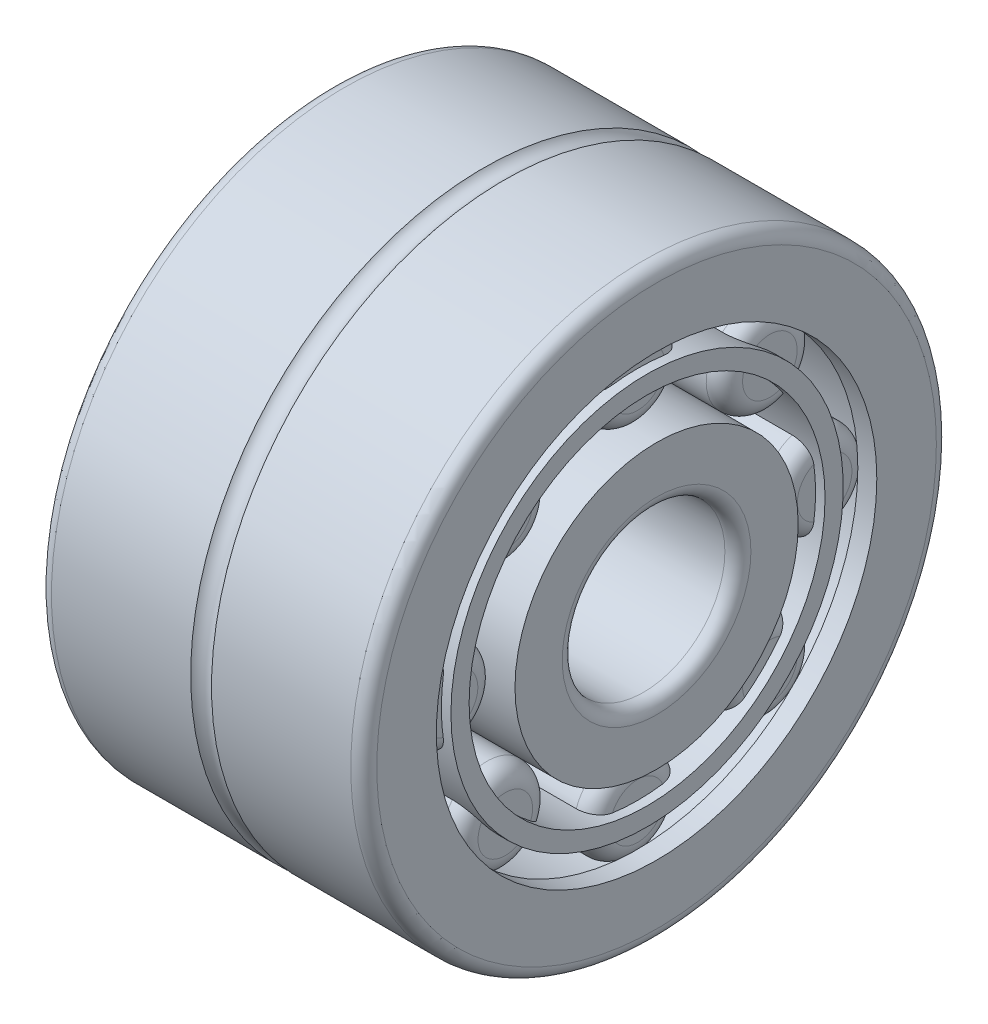
SolidWorks part; units mm, degrees
ref_plane "Plane1" through (0, 0, 0) normal (0, 0, 1) x (1, 0, 0)
ref_plane "Plane2" through (0, 0, 0) normal (0, 1, 0) x (1, 0, 0)
ref_plane "Plane3" through (0, 0, 0) normal (1, 0, 0) x (0, 0, -1)
sketch "Clipboard" plane through (0, 0, 0) normal (0, 0, 1) x (1, 0, 0)
  line L0 (-10, 0) -> (10, 0) construction
  line L1 (0, 0) -> (27.3694, -3.8465)
  line L2 (0, 0) -> (36.1572, 5.0816)
  line L3 (0, 0) -> (44.9449, -6.3166)
  line L4 (0, 0) -> (-22.3471, -0.7804)
  dimension "Race_OD" = 45.3866
  dimension "Race_ID" = 27.6384
sketch "OutRacSke" plane through (0, 0, 0) normal (0, 0, 1) x (1, 0, 0)
  line L0 (-14.0229, 22.6933) -> (-14.0229, 21.4933)
  line L1 (-14.0229, 21.4933) -> (-15.875, 21.4933)
  line L2 (-15.875, 21.4933) -> (-15.875, 27.305)
  line L3 (-14.605, 28.575) -> (-1.016, 28.575)
  line L4 (15.875, 27.305) -> (15.875, 21.4933)
  line L5 (15.875, 21.4933) -> (14.0229, 21.4933)
  line L6 (14.0229, 21.4933) -> (14.0229, 22.6933)
  line L7 (14.0229, 22.6933) -> (-14.0229, 22.6933)
  line L8 (-7.9375, 0) -> (7.9375, 0) construction
  line L9 (1.016, 28.575) -> (14.605, 28.575)
  arc A0 (-15.875, 27.305) -> (-14.605, 28.575) centre (-14.605, 27.305) cw
  arc A1 (14.605, 28.575) -> (15.875, 27.305) centre (14.605, 27.305) cw
  arc A2 (-1.016, 28.575) -> (1.016, 28.575) centre (0, 29.337) ccw
  dimension "D1" = 14.0229
  dimension "Groove_Dp" = 1.2
  dimension "Race_OD" = 45.3866
  dimension "D2" = 0.762
  dimension "Cyl_Len" = 28.0458
  dimension "halfWidth" = 15.875
revolve "OuterRace" add sketch "OutRacSke" angle 360 about L8 reverse direction yes
sketch "RolDetSke" plane through (0, 0, 0) normal (0, 0, 1) x (1, 0, 0)
  line L0 (-14.0229, 20.9188) -> (-14.0229, 18.2562)
  line L1 (-14.0229, 18.2562) -> (14.0229, 18.2562)
  line L2 (14.0229, 18.2562) -> (14.0229, 20.9188)
  line L3 (12.2479, 22.6938) -> (-12.2479, 22.6938)
  line L4 (-28.575, 18.2562) -> (28.575, 18.2562) construction
  arc A0 (14.0229, 20.9188) -> (12.2479, 22.6938) centre (12.2479, 20.9188) ccw
  arc A1 (-12.2479, 22.6938) -> (-14.0229, 20.9188) centre (-12.2479, 20.9188) ccw
  dimension "Cyl_Len" = 28.0458
  dimension "radius" = 1.775
  dimension "Roller_diameter" = 8.8751
revolve "RollerDetailed" add sketch "RolDetSke" angle 360 about L4 reverse direction yes
ref_axis "Axis1" through (-50, 0, 0) along (1, 0, 0)
sketch "RolSimSke" plane through (0, 25.4, 0) normal (0, 0, 1) x (1, 0, 0)
  line L0 (-14.0229, -4.4807) -> (-14.0229, -9.8058)
  line L1 (-25.4, -25.4) -> (25.4, -25.4) construction
  line L2 (14.0229, -9.8058) -> (14.0229, -4.4807)
  line L3 (12.2479, -2.7057) -> (-12.2479, -2.7057)
  line L5 (12.2479, -11.5808) -> (-12.2479, -11.5808)
  arc A0 (14.0229, -4.4807) -> (12.2479, -2.7057) centre (12.2479, -4.4807) ccw
  arc A1 (-12.2479, -2.7057) -> (-14.0229, -4.4807) centre (-12.2479, -4.4807) ccw
  arc A2 (14.0229, -9.8058) -> (12.2479, -11.5808) centre (12.2479, -9.8058) cw
  arc A3 (-12.2479, -11.5808) -> (-14.0229, -9.8058) centre (-12.2479, -9.8058) cw
  dimension "radius" = 1.775
  dimension "Roller_diameter" = 8.8751
  dimension "Cyl_Len" = 28.0458
revolve "RollersSimplified" [suppressed] add sketch "RolSimSke" angle 360 about L1
sketch "InsRacSke" plane through (0, 0, 0) normal (0, 0, 1) x (1, 0, 0)
  line L2 (-15.875, 13.8192) -> (-15.875, 9.2075)
  line L4 (-14.605, 7.9375) -> (14.605, 7.9375)
  line L5 (15.875, 9.2075) -> (15.875, 13.8192)
  line L8 (15.875, 13.8192) -> (-15.875, 13.8192)
  line L9 (-7.9375, 0) -> (7.9375, 0) construction
  arc A0 (-15.875, 9.2075) -> (-14.605, 7.9375) centre (-14.605, 9.2075) ccw
  arc A2 (14.605, 7.9375) -> (15.875, 9.2075) centre (14.605, 9.2075) ccw
  dimension "radius" = 1.27
  dimension "Bore" = 15.875
  dimension "halfWidth" = 15.875
  dimension "Race_ID" = 27.6384
revolve "InnerRace" add sketch "InsRacSke" angle 360 about L9 reverse direction yes
sketch "CagSpiSke" plane through (0, 0, 0) normal (0, 0, 1) x (1, 0, 0)
  line L0 (-17.1595, 0) -> (17.1595, 0) construction
  line L3 (-14.949, 17.3687) -> (14.949, 17.3687)
  line L4 (-14.949, 17.3687) -> (-14.949, 19.1438)
  line L5 (-14.949, 19.1438) -> (14.949, 19.1438)
  line L6 (14.949, 17.3687) -> (14.949, 19.1438)
revolve "CageSpine" add sketch "CagSpiSke" angle 360 about L0
pattern_circular "RollersDetailed" count 8 every 45 about axis through (-50, 0, 0) along (1, 0, 0) of "RollerDetailed"
equation "\"halfWidth@OutRacSke\" =  \"Width@OutRacSke\" / 2"
equation "\"CLdia@Clipboard\" =  ( \"Race_OD@Clipboard\" + \"Race_ID@Clipboard\" )  / 2"
equation "\"CLRad@RolDetSke\" = ( \"Race_OD@Clipboard\" + \"Race_ID@Clipboard\" )  / 4"
equation "\"Roller_diameter@RolDetSke\" =  ( \"Race_OD@Clipboard\" -  \"Race_ID@Clipboard\" )  / 2 + .001"
equation "\"Roller_diameter@RolSimSke\" = ( \"Race_OD@Clipboard\" -  \"Race_ID@Clipboard\" )  / 2 + .001"
equation "\"radius@RolDetSke\" = \"Roller_diameter@RolDetSke\" / 5"
equation "\"radius@RolSimSke\" = \"Roller_diameter@RolSimSke\" / 5"
equation "\"Cyl_Len@OutRacSke\" = \"Cyl_Len@RolDetSke\""
equation "\"Cyl_Len@RolSimSke\" = \"Cyl_Len@RolDetSke\""
equation "\"halfCylLen@RolDetSke\" = \"Cyl_Len@RolDetSke\" / 2"
equation "\"D1@OutRacSke\" = \"Cyl_Len@OutRacSke\" / 2"
equation "\"D2@OutRacSke\" = \"Radius@OutRacSke\" * .6"
equation "\"cage_width@CagSpiSke\" =  ( \"Cyl_Len@RolDetSke\" + \"Width@OutRacSke\" )  / 2"
equation "\"halfwidth@CagSpiSke\" = \"cage_width@CagSpiSke\" / 2"
equation "\"cage_thickness@CagSpiSke\" = \"Roller_diameter@RolDetSke\" / 5"
equation "\"d2@CagSpiSke\" = \"CLRad@RolDetSke\" * 2 - \"cage_thickness@CagSpiSke\""
equation "\"Max_count@Clipboard\" = int( 3.14159265 / atn(( \"Roller_diameter@RolDetSke\" / 2) / sqr( \"CLRad@RolDetSke\"  *  \"CLRad@RolDetSke\" - ( \"Roller_diameter@RolDetSke\" / 2) *  ( \"Roller_diameter@RolDetSke\" / 2))))"
equation "\"Max_count@Clipboard\" = ((sgn( \"Max_count@Clipboard\" - \"Count@Clipboard\" )-1)*( \"Max_count@Clipboard\" - \"Count@Clipboard\" ))/-2+ \"Count@Clipboard\""
equation "\"Count@RollersDetailed\" = int( \"Show_count@Clipboard\" ) "
equation "\"Count@RollersDetailed\" = ((sgn( \"Count@RollersDetailed\" - \"Max_count@Clipboard\" )-1)*( \"Count@RollersDetailed\" - \"Max_count@Clipboard\" ))/-2+ \"Max_count@Clipboard\""
equation "\"Count@RollersDetailed\" = ((sgn( \"Count@RollersDetailed\" - \"Min_count@Clipboard\" )+1)*( \"Count@RollersDetailed\" - \"Min_count@Clipboard\"))/2 +\"Min_count@Clipboard\""
equation "\"Angle@RollersDetailed\" = 360.0 / \"Max_count@Clipboard\""
equation "\"Bore@RolSimSke\" = \"Race_ID@Clipboard\""
equation "\"Race_ID@InsRacSke\" = \"Race_ID@Clipboard\""
equation "\"halfWidth@InsRacSke\" = \"Width_IR@InsRacSke\" / 2"
equation "\"halfLength@RolSimSke\" = \"Cyl_Len@RolSimSke\" / 2"
equation "\"Race_OD@OutRacSke\" = \"Race_OD@Clipboard\""
equation "\"Width_IR@InsRacSke\" = \"Width@OutRacSke\""
equation "\"Angle@CageSpine\" =  \"Angle@RollersDetailed\" * ( \"Count@RollersDetailed\" -1 + int( \"Count@RollersDetailed\" / \"Max_count@Clipboard\" ) )  + 0.001 -  int( \"Count@RollersDetailed\" / \"Max_count@Clipboard\" ) * 0.001"
equation "\"Angle@CageSpine\" =  \"Angle@CageSpine\" * int( \"Min_count@Clipboard\" / 2) + int(1 / \"Min_count@Clipboard\")  * 0.001"
equation "\"radius@InsRacSke\" = \"Radius@OutRacSke\""
